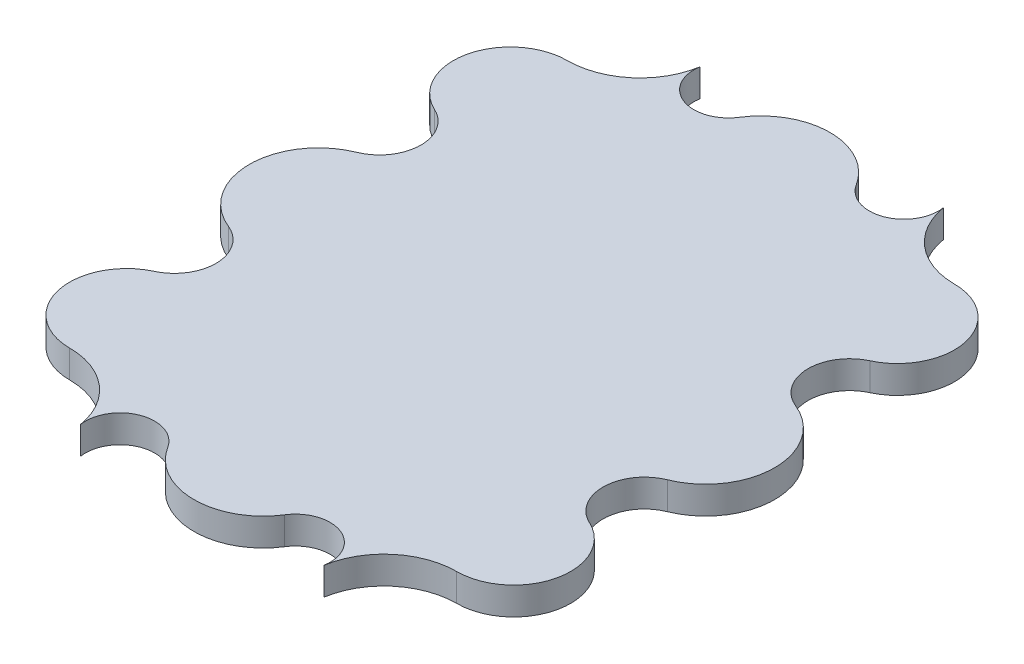
SolidWorks part; units mm, degrees
ref_plane "Alzado" through (0, 0, 0) normal (0, 0, 1) x (1, 0, 0)
ref_plane "Planta" through (0, 0, 0) normal (0, 1, 0) x (1, 0, 0)
ref_plane "Vista lateral" through (0, 0, 0) normal (1, 0, 0) x (0, 0, -1)
sketch "Croquis1" plane through (0, 0, 0) normal (0, 1, 0) x (1, 0, 0)
  line L0 (0, 138.5041) -> (0, -177.2184) construction
  line L2 (-70, -90) -> (-70, 90)
  line L4 (70, -90) -> (70, 90)
  line L5 (-70, -90) -> (70, 90) construction
  line L6 (-70, 90) -> (70, -90) construction
  line L7 (-103.4324, 0) -> (144.2109, 0) construction
  arc A1 (-21.1476, -103.3333) -> (21.1476, -103.3333) centre (0, -90) ccw
  arc A5 (-21.1476, -103.3333) -> (-44.0559, -112.0276) centre (-31.7214, -110) ccw
  arc A6 (-44.0559, -112.0276) -> (-70, -90) centre (-70, -116.2923) ccw
  arc A7 (21.1476, -103.3333) -> (44.0559, -112.0276) centre (31.7214, -110) cw
  arc A8 (44.0559, -112.0276) -> (70, -90) centre (70, -116.2923) cw
  arc A9 (44.0559, 112.0276) -> (70, 90) centre (70, 116.2923) ccw
  arc A10 (21.1476, 103.3333) -> (44.0559, 112.0276) centre (31.7214, 110) ccw
  arc A11 (-21.1476, 103.3333) -> (21.1476, 103.3333) centre (0, 90) cw
  arc A12 (-21.1476, 103.3333) -> (-44.0559, 112.0276) centre (-31.7214, 110) cw
  arc A13 (-44.0559, 112.0276) -> (-70, 90) centre (-70, 116.2923) cw
  point P0 (0, 0)
  point P14 (-25, -90)
  point P16 (-70, -90)
  dimension "D4" = 50
  dimension "D6" = 25
  dimension "D1" = 140
  dimension "D2" = 180
extrude "Saliente-Extruir1" add sketch "Croquis1" along normal blind 10
sketch "Croquis2" plane through (0, 10, 0) normal (0, 1, 0) x (1, 0, 0)
  line L0 (70, -90) -> (70, 90) construction
  line L1 (70, 90) -> (70, -90)
  line L2 (0, 152.4123) -> (0, -148.5895) construction
  line L3 (-96.3545, 0) -> (168.0513, 0) construction
  line L4 (-70, 90) -> (-70, -90)
  arc A0 (79.375, -23.1756) -> (79.375, 23.1756) centre (70, 0) ccw
  arc A1 (78.6826, 50.6858) -> (79.375, 23.1756) centre (85, 37.081) ccw
  arc A2 (78.6826, 50.6858) -> (70, 90) centre (70, 69.3841) ccw
  arc A3 (78.6826, -50.6858) -> (79.375, -23.1756) centre (85, -37.081) cw
  arc A4 (78.6826, -50.6858) -> (70, -90) centre (70, -69.3841) cw
  arc A5 (-78.6826, -50.6858) -> (-70, -90) centre (-70, -69.3841) ccw
  arc A6 (-78.6826, -50.6858) -> (-79.375, -23.1756) centre (-85, -37.081) ccw
  arc A7 (-79.375, -23.1756) -> (-79.375, 23.1756) centre (-70, 0) cw
  arc A8 (-78.6826, 50.6858) -> (-79.375, 23.1756) centre (-85, 37.081) cw
  arc A9 (-78.6826, 50.6858) -> (-70, 90) centre (-70, 69.3841) cw
  line M11 (-70, 90) -> (-70, -90)
  line M17 (70, -90) -> (70, 90)
  dimension "D1" = 50
  dimension "D2" = 30
extrude "Saliente-Extruir2" add sketch "Croquis2" against normal blind 10 contours A9 A8 M11 | A1 A2 L1 | L1 A3 A0 A1 | L4 A8 A7 A6 | A6 A5 L4 | A4 A3 M17 region at (78.5318, 10, -68.6447) region at (78.5318, 10, 68.6447) region at (80.2052, 10, 0) region at (-78.5318, 10, 68.6447) region at (-80.2052, 10, 0) region at (-78.5318, 10, -68.6447)
